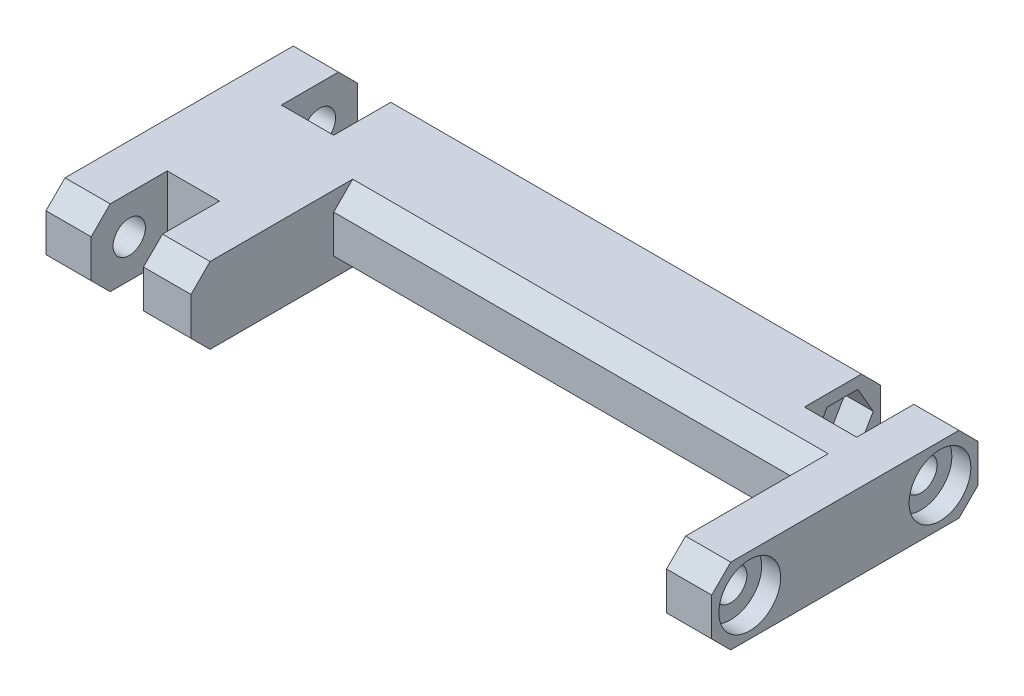
SolidWorks part; units mm, degrees
ref_plane "Front Plane" through (0, 0, 0) normal (0, 0, 1) x (1, 0, 0)
ref_plane "Top Plane" through (0, 0, 0) normal (0, 1, 0) x (1, 0, 0)
ref_plane "Right Plane" through (0, 0, 0) normal (1, 0, 0) x (0, 0, -1)
sketch "Sketch1" plane through (0, 0, 0) normal (0, 1, 0) x (1, 0, 0)
  line L1 (-35, -14) -> (35, -14)
  line L2 (-35, -14) -> (-35, 14)
  line L3 (-35, 14) -> (35, 14)
  line L4 (35, -14) -> (35, 14)
  line L5 (-35, -14) -> (35, 14) construction
  line L6 (-35, 14) -> (35, -14) construction
  point P0 (0, 0)
  dimension "D1" = 70
  dimension "D2" = 28
extrude "Boss-Extrude1" add sketch "Sketch1" along normal blind 8
sketch "Sketch2" plane through (0, 8, 0) normal (0, 1, 0) x (1, 0, 0)
  line L0 (35, 14) -> (-35, 14) construction
  line L1 (-30.25, 14) -> (-24.75, 14)
  line L2 (-30.25, 14) -> (-30.25, 6)
  line L3 (-30.25, 6) -> (-24.75, 6)
  line L4 (-24.75, 14) -> (-24.75, 6)
  line L5 (0, 0) -> (0, 14) construction
  line L6 (24.75, 14) -> (24.75, 6)
  line L7 (30.25, 6) -> (24.75, 6)
  line L8 (30.25, 14) -> (30.25, 6)
  line L9 (30.25, 14) -> (24.75, 14)
  dimension "D1" = 5.5
  dimension "D2" = 8
  dimension "D3" = 49.5
extrude "Cut-Extrude1" cut sketch "Sketch2" against normal through all
hole_wizard "CBORE for M3 Cheese Head Screw1" positions "Sketch7" profile "Sketch8" counterbore size "M3" standard "ISO" end condition up to next
sketch "Sketch7" plane through (35, 0, 0) normal (1, 0, 0) x (0, 0, -1)
  line L0 (-14, 8) -> (14, 8) construction
  line L1 (14, 8) -> (14, 0) construction
  point P0 (10, 4)
  dimension "D1" = 4
  dimension "D2" = 4
sketch "Sketch8" plane through (35, 4, -10) normal (0, 1, 0) x (0, 0, -1)
  line L0 (0, 0) -> (0, 56.75)
  line L1 (0, 56.75) -> (1.7, 56.75)
  line L3 (1.7, 56.75) -> (1.7, 2)
  line L4 (1.7, 2) -> (3.25, 2)
  line L5 (3.25, 2) -> (3.25, 0)
  line L7 (3.25, 0) -> (0, 0)
  line L11 (0, -6.35) -> (0, 107.95) construction
  dimension "Thru Hole Dia." = 3.4
  dimension "Thru Hole Depth" = 56.75
  dimension "C'Bore Dia." = 6.5
  dimension "C'Bore Depth" = 2
sketch "Sketch9" plane through (24.75, 0, 0) normal (1, 0, 0) x (0, 0, -1)
  line L1 (11.6166, 6.8) -> (8.3834, 6.8)
  line L2 (8.3834, 6.8) -> (6.7668, 4)
  line L3 (6.7668, 4) -> (8.3834, 1.2)
  line L4 (8.3834, 1.2) -> (11.6166, 1.2)
  line L5 (11.6166, 1.2) -> (13.2332, 4)
  line L6 (13.2332, 4) -> (11.6166, 6.8)
  circle A0 centre (10, 4) radius 2.8 construction
  dimension "D1" = 5.6
extrude "Cut-Extrude2" cut sketch "Sketch9" against normal blind 3
mirror "Mirror1" about plane through (0, 0, 0) normal (1, 0, 0) of "Cut-Extrude2", "CBORE for M3 Cheese Head Screw1"
mirror "Mirror2" about plane through (0, 0, 0) normal (0, 0, 1) of "Cut-Extrude1", "CBORE for M3 Cheese Head Screw1", "Cut-Extrude2", "Mirror1"
chamfer "Chamfer1" distance 2 angle 45 12 edges at (32.625, 0, -14) (32.625, 8, -14) (0, 0, -14) (0, 8, -14) (-32.625, 0, -14) (-32.625, 8, -14) (-32.625, 0, 14) (32.625, 0, 14) (0, 0, 14) (32.625, 8, 14) (-32.625, 8, 14) (0, 8, 14)
sketch "Sketch10" plane through (0, 8, 0) normal (0, 1, 0) x (1, 0, 0)
  line L0 (24.75, -14) -> (-24.75, -14) construction
  line L1 (-19.75, -14) -> (30.25, -14)
  line L2 (-19.75, -14) -> (-19.75, 1)
  line L3 (-19.75, 1) -> (30.25, 1)
  line L4 (30.25, -14) -> (30.25, 1)
  line L5 (30.25, -6) -> (30.25, -12) construction
  line L6 (-24.75, -6) -> (-24.75, -12) construction
  dimension "D1" = 5
  dimension "D2" = 15
extrude "Cut-Extrude3" cut sketch "Sketch10" against normal through all
chamfer "Chamfer2" distance 2 angle 45 2 edges at (5.25, 0, -1) (5.25, 8, -1)
